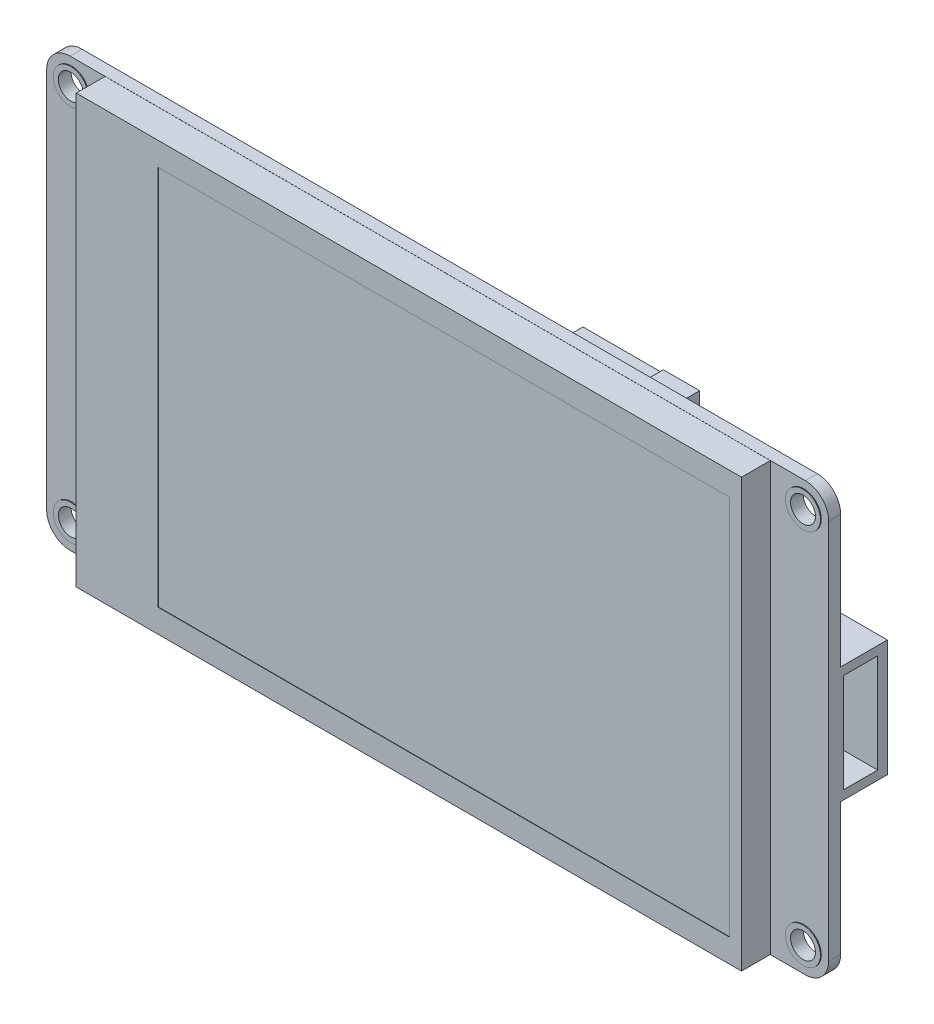
SolidWorks part; units mm, degrees
ref_plane "Front Plane" through (0, 0, 0) normal (0, 0, 1) x (1, 0, 0)
ref_plane "Top Plane" through (0, 0, 0) normal (0, 1, 0) x (1, 0, 0)
ref_plane "Right Plane" through (0, 0, 0) normal (1, 0, 0) x (0, 0, -1)
sketch "Sketch1" plane through (0, 0, 0) normal (0, 0, 1) x (1, 0, 0)
  line L1 (-47.25, 27.5) -> (47.25, 27.5)
  line L2 (-50.25, 24.5) -> (-50.25, -24.5)
  line L3 (-47.25, -27.5) -> (47.25, -27.5)
  line L4 (50.25, 24.5) -> (50.25, -24.5)
  line L5 (-50.25, 27.5) -> (50.25, -27.5) construction
  line L6 (-50.25, -27.5) -> (50.25, 27.5) construction
  arc A0 (47.25, -27.5) -> (50.25, -24.5) centre (47.25, -24.5) ccw
  arc A1 (47.25, 27.5) -> (50.25, 24.5) centre (47.25, 24.5) cw
  arc A2 (-47.25, 27.5) -> (-50.25, 24.5) centre (-47.25, 24.5) ccw
  arc A3 (-50.25, -24.5) -> (-47.25, -27.5) centre (-47.25, -24.5) ccw
  point P0 (0, 0)
  dimension "D3" = 3
  dimension "D1" = 100.5
  dimension "D2" = 55
extrude "Boss-Extrude1" add sketch "Sketch1" along normal blind 1.54
hole_wizard "Ø3.2 (3.2) Diameter Hole1" positions "Sketch3" profile "Sketch2" hole size "Ø3.2" standard "DIN" end condition through all
sketch "Sketch3" plane through (0, 0, 1.54) normal (0, 0, 1) x (1, 0, 0)
  line L0 (-47.05, 24.25) -> (47.05, 24.25) construction
  line L1 (47.05, 24.25) -> (47.05, -24.25) construction
  line L2 (47.05, -24.25) -> (-47.05, -24.25) construction
  line L3 (-47.05, -24.25) -> (-47.05, 24.25) construction
  line L6 (0, 24.25) -> (0, -24.25) construction
  line L9 (-47.05, 0) -> (47.05, 0) construction
  point P0 (-47.05, 24.25)
  point P2 (47.05, 24.25)
  point P4 (47.05, -24.25)
  point P6 (-47.05, -24.25)
  dimension "D1" = 94.1
  dimension "D2" = 48.5
sketch "Sketch2" plane through (-47.05, 24.25, 1.54) normal (1, 0, 0) x (0, -1, 0)
  line L0 (0, 0) -> (0, 1.54)
  line L1 (0, 1.54) -> (1.6, 1.54)
  line L2 (1.6, 1.54) -> (1.6, 0)
  line L5 (1.6, 0) -> (0, 0)
  line L11 (0, -6.35) -> (0, 107.95) construction
  dimension "Thru Hole Dia." = 3.2
  dimension "Thru Hole Depth" = 1.54
sketch "Sketch4" plane through (0, 0, 1.54) normal (0, 0, 1) x (1, 0, 0)
  circle A0 centre (-47.05, 24.25) radius 1.6
  circle A1 centre (-47.05, 24.25) radius 2.25
  circle A2 centre (47.05, 24.25) radius 1.6
  circle A3 centre (47.05, -24.25) radius 1.6
  circle A4 centre (-47.05, -24.25) radius 1.6
  circle A5 centre (-47.05, -24.25) radius 2.25
  circle A6 centre (47.05, -24.25) radius 2.25
  circle A7 centre (47.05, 24.25) radius 2.25
  dimension "D1" = 4.5
extrude "Boss-Extrude2" add sketch "Sketch4" along normal blind 0.1
sketch "Sketch5" plane through (0, 0, 1.54) normal (0, 0, 1) x (1, 0, 0)
  line L1 (-42.75, 27.4847) -> (42.75, 27.4847)
  line L2 (-42.75, 27.4847) -> (-42.75, -27.4847)
  line L3 (-42.75, -27.4847) -> (42.75, -27.4847)
  line L4 (42.75, 27.4847) -> (42.75, -27.4847)
  line L5 (-42.75, 27.4847) -> (42.75, -27.4847) construction
  line L6 (-42.75, -27.4847) -> (42.75, 27.4847) construction
  point P0 (0, 0)
  dimension "D1" = 85.5
extrude "Boss-Extrude3" add sketch "Sketch5" along normal blind 3.7
sketch "Sketch6" plane through (0, 0, 5.24) normal (0, 0, 1) x (1, 0, 0)
  line L0 (0, 0) -> (4.48, 0) construction
  line L1 (-32.24, 24.48) -> (41.2, 24.48)
  line L2 (-32.24, 24.48) -> (-32.24, -24.48)
  line L3 (-32.24, -24.48) -> (41.2, -24.48)
  line L4 (41.2, 24.48) -> (41.2, -24.48)
  line L5 (-32.24, 24.48) -> (41.2, -24.48) construction
  line L6 (-32.24, -24.48) -> (41.2, 24.48) construction
  point P0 (4.48, 0)
  dimension "D1" = 4.48
  dimension "D2" = 73.44
  dimension "D3" = 48.96
extrude "Cut-Extrude1" cut sketch "Sketch6" against normal blind 0.05
sketch "Sketch7" plane through (50.25, 0, 0) normal (1, 0, 0) x (0, 0, -1)
  line L0 (0, -24.5) -> (0, 24.5) construction
  line L1 (6, 7.5) -> (0, 7.5)
  line L2 (6, 7.5) -> (6, -7.5)
  line L3 (6, -7.5) -> (0, -7.5)
  line L4 (0, 7.5) -> (0, -7.5)
  line L5 (6, 7.5) -> (0, -7.5) construction
  line L6 (6, -7.5) -> (0, 7.5) construction
  point P0 (3, 0)
  dimension "D1" = 6
  dimension "D2" = 15
extrude "Boss-Extrude4" add sketch "Sketch7" against normal blind 7.1
sketch "Sketch8" plane through (50.25, 0, 0) normal (1, 0, 0) x (0, 0, -1)
  line L1 (0.3388, 6.3578) -> (4.7572, 6.3578)
  line L2 (0.3388, 6.3578) -> (0.3388, -6.3578)
  line L3 (0.3388, -6.3578) -> (4.7572, -6.3578)
  line L4 (4.7572, 6.3578) -> (4.7572, -6.3578)
  line L5 (0.3388, 6.3578) -> (4.7572, -6.3578) construction
  line L6 (0.3388, -6.3578) -> (4.7572, 6.3578) construction
  point P0 (2.548, 0)
extrude "Cut-Extrude2" cut sketch "Sketch8" against normal blind 6
sketch "Sketch9" plane through (0, 0, 0) normal (0, 0, -1) x (-1, 0, 0)
  line L1 (-30.25, 12.3) -> (-15.25, 12.3)
  line L2 (-30.25, 12.3) -> (-30.25, 27.3)
  line L3 (-30.25, 27.3) -> (-25.5826, 27.3)
  line L4 (-15.25, 12.3) -> (-15.25, 26.9)
  line L5 (-30.25, 12.3) -> (-15.25, 27.3) construction
  line L6 (-30.25, 27.3) -> (-15.25, 12.3) construction
  line L7 (-50.25, 7.5) -> (-50.25, 24.5) construction
  line L8 (-47.25, 27.5) -> (47.25, 27.5) construction
  line L9 (-15.25, 26.9) -> (-25.2326, 26.9)
  line L10 (-25.5826, 27.25) -> (-25.5826, 27.3)
  arc A0 (-25.2326, 26.9) -> (-25.5826, 27.25) centre (-25.2326, 27.25) cw
  point P0 (-22.75, 19.8)
  dimension "D6" = 0.35
  dimension "D1" = 15
  dimension "D2" = 15
  dimension "D3" = 20
  dimension "D4" = 0.2
  dimension "D5" = 0.4
extrude "Boss-Extrude5" add sketch "Sketch9" along normal blind 1.88
sketch "Sketch18" plane through (0, 0, 5.19) normal (0, 0, 1) x (1, 0, 0)
  line L0 (-30.4421, 0) -> (28.9205, 0) construction
sketch "Sketch19" plane through (0, 0, 5.19) normal (0, 0, 1) x (1, 0, 0)
  text T0 "www.apronecs.bg"
extrude "Boss-Extrude6" [suppressed] add sketch "Sketch19" along normal blind 0.01
